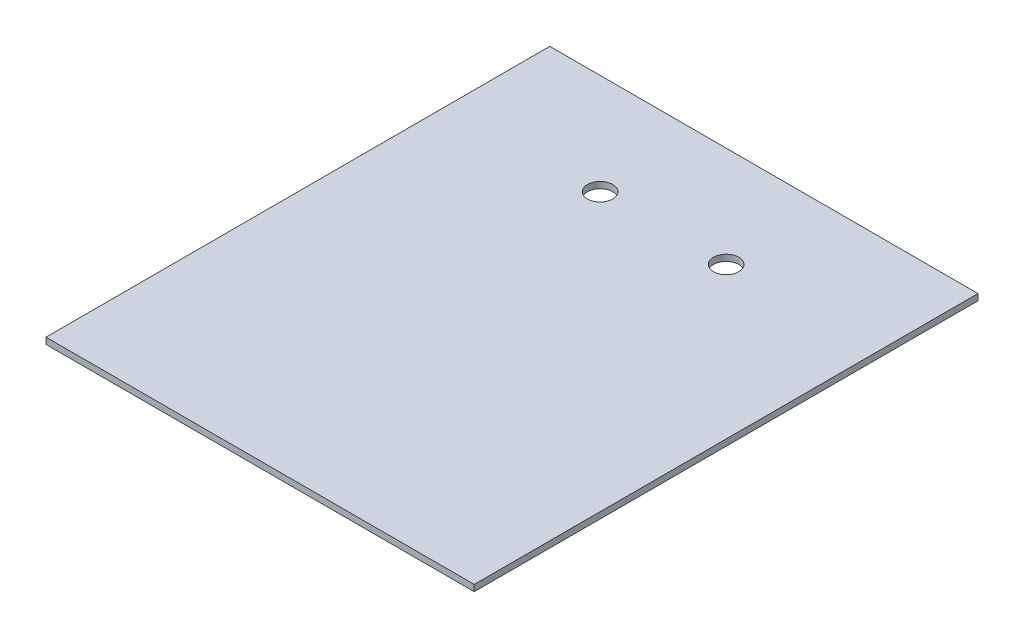
SolidWorks part; units mm, degrees
ref_plane "Front Plane" through (0, 0, 0) normal (0, 0, 1) x (1, 0, 0)
ref_plane "Top Plane" through (0, 0, 0) normal (0, 1, 0) x (1, 0, 0)
ref_plane "Right Plane" through (0, 0, 0) normal (1, 0, 0) x (0, 0, -1)
sketch "Sketch1" plane through (0, 0, 0) normal (0, 1, 0) x (1, 0, 0)
  line L1 (0, 0) -> (215.9, 0)
  line L2 (0, 0) -> (0, 254)
  line L3 (0, 254) -> (215.9, 254)
  line L4 (215.9, 0) -> (215.9, 254)
  dimension "D1" = 254
  dimension "D2" = 215.9
extrude "Boss-Extrude1" add sketch "Sketch1" along normal blind 3.175
sketch "Sketch2" plane through (0, 3.175, 0) normal (0, 1, 0) x (1, 0, 0)
  line L0 (0, 203.2) -> (76.2, 203.2) construction
  line L1 (0, 254) -> (0, 0) construction
  line L2 (76.2, 203.2) -> (139.7, 203.2) construction
  line L5 (139.7, 203.2) -> (215.9, 203.2) construction
  line L6 (215.9, 0) -> (215.9, 254) construction
  line L7 (215.9, 254) -> (0, 254) construction
  circle A0 centre (76.2, 203.2) radius 6.35
  circle A1 centre (139.7, 203.2) radius 6.35
  point P7 (60.7355, 204.6354)
  dimension "D1" = 12.7
  dimension "D2" = 50.8
  dimension "D3" = 63.5
extrude "Cut-Extrude1" cut sketch "Sketch2" against normal through all
